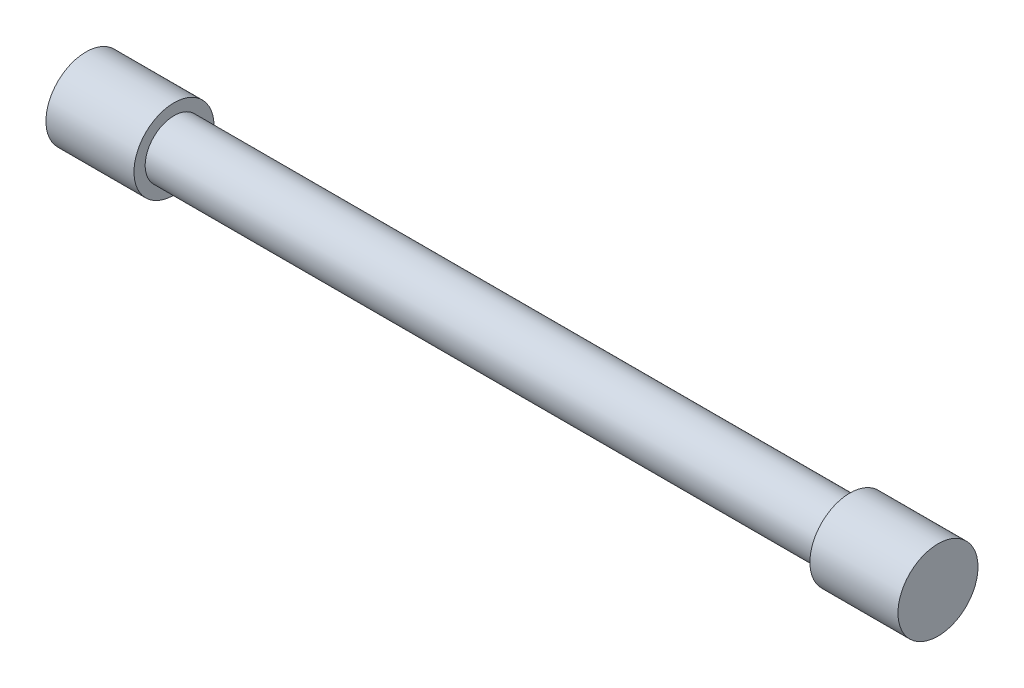
SolidWorks part; units mm, degrees
ref_plane "Front Plane" through (0, 0, 0) normal (0, 0, 1) x (1, 0, 0)
ref_plane "Top Plane" through (0, 0, 0) normal (0, 1, 0) x (1, 0, 0)
ref_plane "Right Plane" through (0, 0, 0) normal (1, 0, 0) x (0, 0, -1)
sketch "Sketch1" plane through (0, 0, 0) normal (1, 0, 0) x (0, 0, -1)
  circle A0 centre (0, 0) radius 9
  circle A1 centre (0, 0) radius 12.5
  dimension "D1" = 18
  dimension "D2" = 25
extrude "Boss-Extrude1" add sketch "Sketch1" along normal blind 27.5
extrude "Boss-Extrude2" add sketch "Sketch1<3>" along normal blind 266.1 contours A0 region at (0, 0, 0)
sketch "Sketch1<3>" plane through (0, 0, 0) normal (1, 0, 0) x (0, 0, -1) same geometry as "Sketch1"
sketch "Sketch2" plane through (266.1, 0, 0) normal (1, 0, 0) x (0, 0, -1)
  circle A0 centre (0, 0) radius 12.5
extrude "Boss-Extrude3" add sketch "Sketch2" against normal blind 27.5
